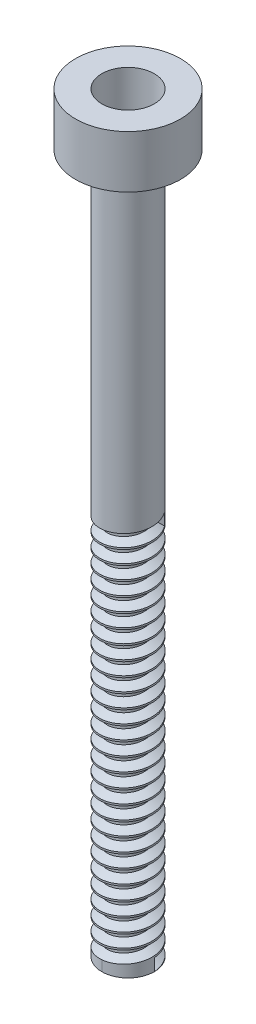
SolidWorks part; units mm, degrees
ref_plane "Front" through (0, 0, 0) normal (0, 0, 1) x (1, 0, 0)
ref_plane "Top" through (0, 0, 0) normal (0, 1, 0) x (1, 0, 0)
ref_plane "Right" through (0, 0, 0) normal (1, 0, 0) x (0, 0, -1)
sketch "Skizze1" plane through (0, 0, 0) normal (0, 1, 0) x (1, 0, 0)
  circle A0 centre (0, 0) radius 3
  circle A1 centre (0, 0) radius 1.5
extrude "Aufsatz-Linear austragen1" add sketch "Skizze1" against normal blind 40 contours A1
extrude "Aufsatz-Linear austragen2" add sketch "Skizze1<3>" along normal blind 3 separate body
sketch "Skizze1<3>" plane through (0, 0, 0) normal (0, 1, 0) x (1, 0, 0) same geometry as "Skizze1"
thread "Gewinde1" pitch 0.7937 method cut profile "Gewindeprofil1" start angle 0, offset 0, length 0, pitch 0.7937, diameter 3
ref_plane "Ebene1" through (1.5, -40, 0) normal (0, 0, 1) x (1, 0, 0)
sketch "Gewindeprofil1" plane through (1.5, -40, 0) normal (0, 0, 1) x (1, 0, 0)
  line L0 (0, 0) -> (0, 0.7937) construction
  line L11 (0, 0) -> (0, 0.6945)
  line L12 (0, 0.6945) -> (-0.4296, 0.4465)
  line L13 (-0.4296, 0.4465) -> (-0.4296, 0.248)
  line L15 (-0.4296, 0.248) -> (0, 0)
  line L17 (-0.4296, 0.3473) -> (0, 0.3473) construction
  point P2 (0, 0)
  dimension "Pitch" = 0.7937
  dimension "Profile_Angle" = 60
  dimension "Profile_Land" = 0.1984
  dimension "Profile_Height" = 0.4296
